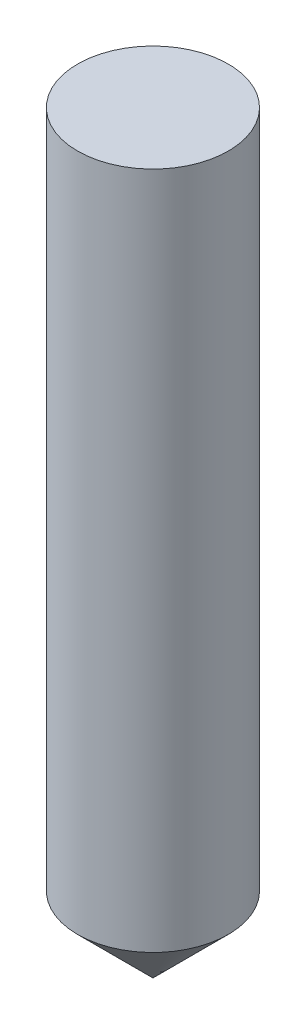
SolidWorks part; units mm, degrees
ref_plane "Front Plane" through (0, 0, 0) normal (0, 0, 1) x (1, 0, 0)
ref_plane "Top Plane" through (0, 0, 0) normal (0, 1, 0) x (1, 0, 0)
ref_plane "Right Plane" through (0, 0, 0) normal (1, 0, 0) x (0, 0, -1)
sketch "Sketch1" plane through (0, 0, 0) normal (0, 1, 0) x (1, 0, 0)
  circle A0 centre (0, 0) radius 5
extrude "Boss-Extrude1" add sketch "Sketch1" along normal blind 50
chamfer "Chamfer1" distance 5 angle 45 1 edges at (0, 0, 5)
ref_axis "Axis1" through (0, 5, 0) along (0, -1, 0)
ref_axis "Axis2" through (0, 50, 0) along (0, -1, 0)
